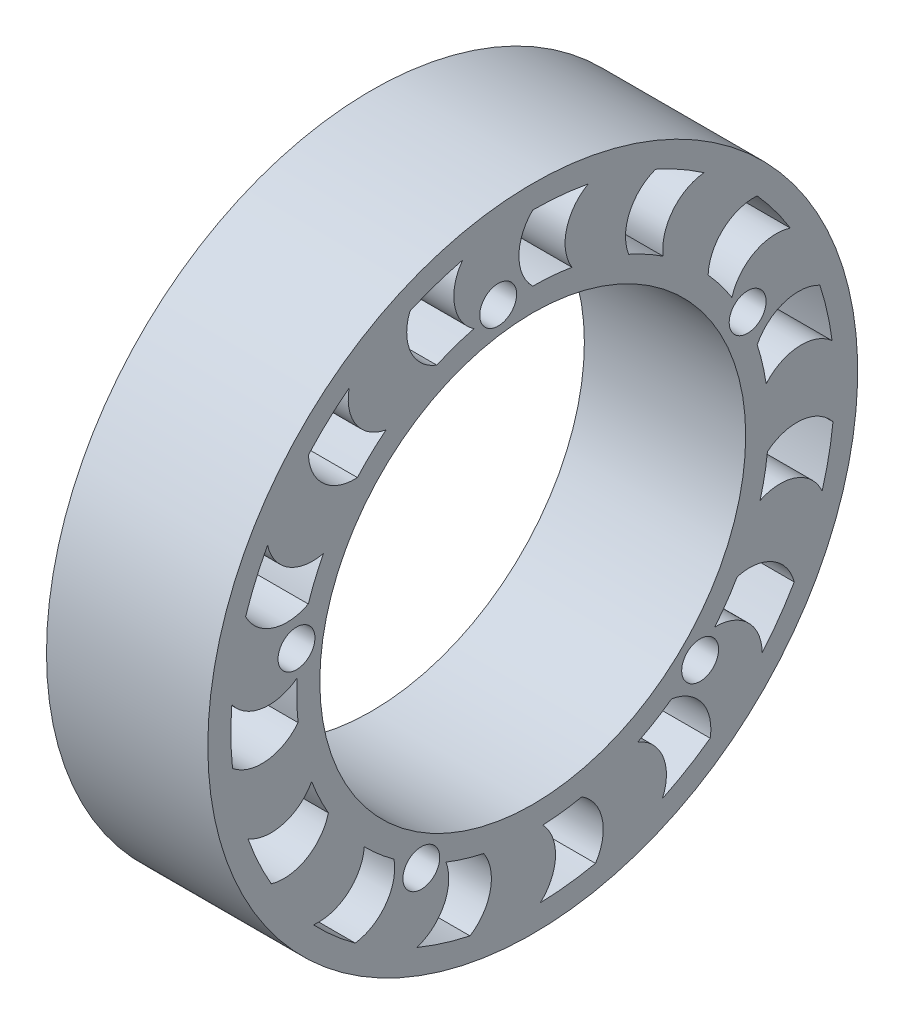
SolidWorks part; units mm, degrees
ref_plane "Front Plane" through (0, 0, 0) normal (0, 0, 1) x (1, 0, 0)
ref_plane "Top Plane" through (0, 0, 0) normal (0, 1, 0) x (1, 0, 0)
ref_plane "Right Plane" through (0, 0, 0) normal (1, 0, 0) x (0, 0, -1)
sketch "Sketch1" plane through (0, 0, 0) normal (0, 1, 0) x (1, 0, 0)
  line L0 (-17.5, 65.5) -> (17.5, 65.5)
  line L4 (17.5, 70.5) -> (-17.5, 70.5)
  line L5 (-17.5, 70.5) -> (-17.5, 65.5)
  line L6 (-1000, 0) -> (49000, 0) construction
  line L7 (17.5, 70.5) -> (17.5, 65.5)
  point P3 (0, 65.5)
  dimension "D1" = 35
  dimension "D2" = 5
  dimension "D4" = 141
revolve "Body" add sketch "Sketch1" angle 360 about L6
sketch "Sketch7" plane through (17.5, 0, 0) normal (-1, 0, 0) x (0, 0, 1)
  arc A1 (0, 65.5) -> (0, 51.2) centre (-6.9912, 58.35) cw
  circle A82 centre (0, 0) radius 46.2
  circle A83 centre (0, 0) radius 65.5 construction
  arc A84 (0, 65.5) -> (-12, 64.3914) centre (0, 0) ccw
  arc A85 (0, 51.2) -> (-8.5, 50.4895) centre (0, 0) ccw
  arc A88 (-12, 64.3914) -> (-8.5, 50.4895) centre (-17.0119, 55.738) cw
  arc A89 (26.6413, 59.8372) -> (20.8249, 46.7735) centre (17.3463, 56.149) cw
  circle A90 centre (0, 0) radius 51.2 construction
  arc A91 (26.6413, 59.8372) -> (15.2278, 63.7053) centre (0, 0) ccw
  arc A92 (20.8249, 46.7735) -> (12.7708, 49.5817) centre (0, 0) ccw
  arc A93 (15.2278, 63.7053) -> (12.7708, 49.5817) centre (7.1295, 57.8386) cw
  arc A94 (48.676, 43.8281) -> (38.049, 34.2595) centre (38.6844, 44.2393) cw
  arc A95 (48.676, 43.8281) -> (39.8226, 52.004) centre (0, 0) ccw
  arc A96 (38.049, 34.2595) -> (31.8334, 40.1008) centre (0, 0) ccw
  arc A97 (39.8226, 52.004) -> (31.8334, 40.1008) centre (30.0382, 49.9383) cw
  arc A98 (62.2942, 20.2406) -> (48.6941, 15.8217) centre (53.3337, 24.6802) cw
  arc A99 (62.2942, 20.2406) -> (57.5316, 31.3107) centre (0, 0) ccw
  arc A100 (48.6941, 15.8217) -> (45.3917, 23.6861) centre (0, 0) ccw
  arc A101 (57.5316, 31.3107) -> (45.3917, 23.6861) centre (47.753, 33.4033) cw
  arc A102 (65.1412, -6.8466) -> (50.9195, -5.3519) centre (58.7611, 0.8537) cw
  arc A103 (65.1412, -6.8466) -> (65.293, 5.2035) centre (0, 0) ccw
  arc A104 (50.9195, -5.3519) -> (51.1014, 3.1758) centre (0, 0) ccw
  arc A105 (65.293, 5.2035) -> (51.1014, 3.1758) centre (57.2109, 11.0925) cw
  arc A106 (56.7247, -32.75) -> (44.3405, -25.6) centre (54.0282, -23.1204) cw
  arc A107 (56.7247, -32.75) -> (61.7646, -21.8034) centre (0, 0) ccw
  arc A108 (44.3405, -25.6) -> (47.9752, -17.8835) centre (0, 0) ccw
  arc A109 (61.7646, -21.8034) -> (47.9752, -17.8835) centre (56.7765, -13.1362) cw
  arc A110 (38.4999, -52.9906) -> (30.0946, -41.4217) centre (39.9533, -43.0968) cw
  arc A111 (38.4999, -52.9906) -> (47.5565, -45.0403) centre (0, 0) ccw
  arc A112 (30.0946, -41.4217) -> (36.5536, -35.8507) centre (0, 0) ccw
  arc A113 (47.5565, -45.0403) -> (36.5536, -35.8507) centre (46.5249, -35.0936) cw
  arc A114 (13.6182, -64.0687) -> (10.6451, -50.0812) centre (18.9701, -55.6214) cw
  arc A115 (13.6182, -64.0687) -> (25.1255, -60.4893) centre (0, 0) ccw
  arc A116 (10.6451, -50.0812) -> (18.8116, -47.6189) centre (0, 0) ccw
  arc A117 (25.1255, -60.4893) -> (18.8116, -47.6189) centre (28.2288, -50.983) cw
  arc A118 (-13.6182, -64.0687) -> (-10.6451, -50.0812) centre (-5.2932, -58.5285) cw
  arc A119 (-13.6182, -64.0687) -> (-1.6499, -65.4792) centre (0, 0) ccw
  arc A120 (-10.6451, -50.0812) -> (-2.1831, -51.1534) centre (0, 0) ccw
  arc A121 (-1.6499, -65.4792) -> (-2.1831, -51.1534) centre (5.0516, -58.057) cw
  arc A122 (-38.4999, -52.9906) -> (-30.0946, -41.4217) centre (-28.6412, -51.3155) cw
  arc A123 (-38.4999, -52.9906) -> (-28.1401, -59.1471) centre (0, 0) ccw
  arc A124 (-30.0946, -41.4217) -> (-22.8003, -45.843) centre (0, 0) ccw
  arc A125 (-28.1401, -59.1471) -> (-22.8003, -45.843) centre (-18.999, -55.0924) cw
  arc A126 (-56.7247, -32.75) -> (-44.3405, -25.6) centre (-47.037, -35.2296) cw
  arc A127 (-56.7247, -32.75) -> (-49.7646, -42.588) centre (0, 0) ccw
  arc A128 (-44.3405, -25.6) -> (-39.4752, -32.606) centre (0, 0) ccw
  arc A129 (-49.7646, -42.588) -> (-39.4752, -32.606) centre (-39.7646, -42.6018) cw
  arc A130 (-65.1412, -6.8466) -> (-50.9195, -5.3519) centre (-57.2996, -13.0522) cw
  arc A131 (-65.1412, -6.8466) -> (-62.7843, -18.665) centre (0, 0) ccw
  arc A132 (-50.9195, -5.3519) -> (-49.3244, -13.731) centre (0, 0) ccw
  arc A133 (-62.7843, -18.665) -> (-49.3244, -13.731) centre (-53.6545, -22.7449) cw
  arc A134 (-62.2942, 20.2406) -> (-48.6941, 15.8217) centre (-57.6546, 11.3821) cw
  arc A135 (-62.2942, 20.2406) -> (-64.948, 8.4854) centre (0, 0) ccw
  arc A136 (-48.6941, 15.8217) -> (-50.645, 7.5181) centre (0, 0) ccw
  arc A137 (-64.948, 8.4854) -> (-50.645, 7.5181) centre (-58.267, 1.0447) cw
  arc A138 (-48.676, 43.8281) -> (-38.049, 34.2595) centre (-48.0406, 33.8483) cw
  arc A139 (-48.676, 43.8281) -> (-55.8817, 34.1685) centre (0, 0) ccw
  arc A140 (-38.049, 34.2595) -> (-43.2086, 27.4673) centre (0, 0) ccw
  arc A141 (-55.8817, 34.1685) -> (-43.2086, 27.4673) centre (-52.8046, 24.6537) cw
  arc A142 (-26.6413, 59.8372) -> (-20.8249, 46.7735) centre (-30.1199, 50.4618) cw
  arc A143 (-26.6413, 59.8372) -> (-37.1529, 53.9436) centre (0, 0) ccw
  arc A144 (-20.8249, 46.7735) -> (-28.3011, 42.6672) centre (0, 0) ccw
  arc A145 (-37.1529, 53.9436) -> (-28.3011, 42.6672) centre (-38.2119, 43.9998) cw
  point P5 (51.25, 0)
  point P99 (0, 0)
  circle M88 centre (0, 0) radius 65.5
  dimension "D1" = 92.4
  dimension "D5" = 10
  dimension "D3" = 12
  dimension "D4" = 8.5
  dimension "D6" = 10
  dimension "D2" = 5
extrude "Reinforcement" add sketch "Sketch7" along normal up to surface (35 mm away) contours A104 A107 A110 M88 region at (17.5, 63.2113, 7.4499) up to face at (-17.5, 0, 65.5)
sketch "Sketch8" plane through (-17.5, 0, 0) normal (-1, 0, 0) x (0, 0, 1)
  circle A0 centre (7.5, 51.4563) radius 4
  circle A1 centre (51.2555, 8.7679) radius 4
  circle A2 centre (24.1776, -46.0374) radius 4
  circle A3 centre (-36.3129, -37.2206) radius 4
  circle A4 centre (-46.6202, 23.0338) radius 4
  circle A5 centre (0, 0) radius 52 construction
  point P14 (0, 0)
  dimension "D1" = 8
  dimension "D3" = 104
  dimension "D2" = 7.5
extrude "Inserts_Holes_A" cut sketch "Sketch8" against normal blind 12.7
mirror "Mirror1" about plane through (0, 0, 0) normal (1, 0, 0) of "Inserts_Holes_A"
